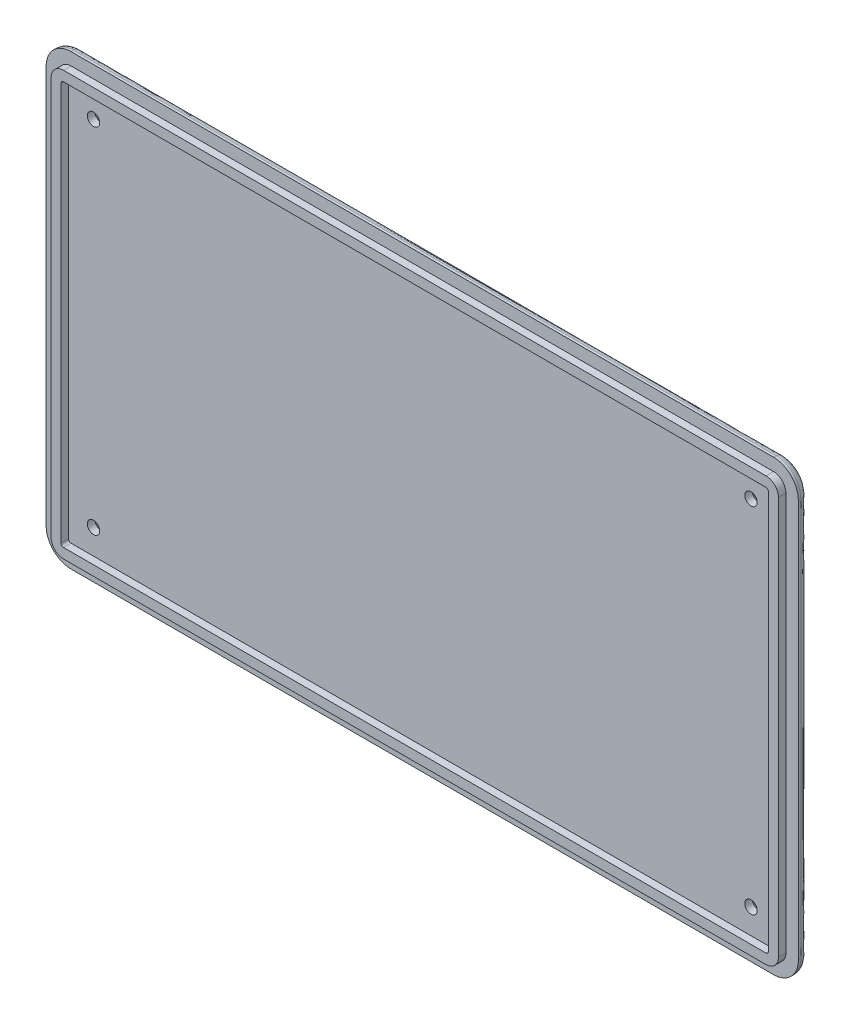
SolidWorks part; units mm, degrees
ref_plane "Спереди" through (0, 0, 0) normal (0, 0, 1) x (1, 0, 0)
ref_plane "Сверху" through (0, 0, 0) normal (0, 1, 0) x (1, 0, 0)
ref_plane "Справа" through (0, 0, 0) normal (1, 0, 0) x (0, 0, -1)
sketch "Эскиз1" plane through (0, 0, 0) normal (0, 0, 1) x (1, 0, 0)
  line L0 (-70.4628, -44.9619) -> (70.4628, -44.9619) construction
  line L1 (75.4619, -39.9628) -> (75.4619, 39.9628) construction
  line L2 (70.4628, 44.9619) -> (-70.4628, 44.9619) construction
  line L3 (-75.4619, 39.9628) -> (-75.4619, -39.9628) construction
  line L4 (-70.4628, -44.9619) -> (70.4628, -44.9619)
  line L5 (75.4619, -39.9628) -> (75.4619, 39.9628)
  line L6 (70.4628, 44.9619) -> (-70.4628, 44.9619)
  line L7 (-75.4619, 39.9628) -> (-75.4619, -39.9628)
  circle A0 centre (65.9619, -35.4619) radius 1.25 construction
  circle A1 centre (65.9619, -35.4619) radius 1.25
  circle A2 centre (65.9619, 35.4619) radius 1.25 construction
  circle A3 centre (65.9619, 35.4619) radius 1.25
  circle A4 centre (-65.9619, -35.4619) radius 1.25 construction
  circle A5 centre (-65.9619, -35.4619) radius 1.25
  circle A6 centre (-65.9619, 35.4619) radius 1.25 construction
  circle A7 centre (-65.9619, 35.4619) radius 1.25
  ellipse E0 centre (-70.4617, -39.9617) end of major axis (-66.926, -36.426) minor radius 5 (-75.4619, -39.9628) -> (-70.4628, -44.9619) ccw construction
  ellipse E1 centre (70.4617, -39.9617) end of major axis (73.9975, -43.4975) minor radius 5 (70.4628, -44.9619) -> (75.4619, -39.9628) ccw construction
  ellipse E2 centre (70.4617, 39.9617) end of major axis (66.926, 36.426) minor radius 5 (75.4619, 39.9628) -> (70.4628, 44.9619) ccw construction
  ellipse E3 centre (-70.4617, 39.9617) end of major axis (-73.9975, 43.4975) minor radius 5 (-70.4628, 44.9619) -> (-75.4619, 39.9628) ccw construction
  ellipse E4 centre (-70.4617, -39.9617) end of major axis (-66.926, -36.426) minor radius 5 (-75.4619, -39.9628) -> (-70.4628, -44.9619) ccw
  ellipse E5 centre (70.4617, -39.9617) end of major axis (73.9975, -43.4975) minor radius 5 (70.4628, -44.9619) -> (75.4619, -39.9628) ccw
  ellipse E6 centre (70.4617, 39.9617) end of major axis (66.926, 36.426) minor radius 5 (75.4619, 39.9628) -> (70.4628, 44.9619) ccw
  ellipse E7 centre (-70.4617, 39.9617) end of major axis (-73.9975, 43.4975) minor radius 5 (-70.4628, 44.9619) -> (-75.4619, 39.9628) ccw
extrude "Бобышка-Вытянуть1" add sketch "Эскиз1" against normal blind 2.5
sketch "Эскиз2" plane through (0, 0, 0) normal (0, 0, 1) x (1, 0, 0)
  line L0 (70.4628, 42.4624) -> (-70.4628, 42.4624) construction
  line L1 (72.9624, -39.9628) -> (72.9624, 39.9628) construction
  line L2 (-70.4628, -42.4624) -> (70.4628, -42.4624) construction
  line L3 (-72.9624, 39.9628) -> (-72.9624, -39.9628) construction
  line L4 (70.4628, 42.4624) -> (-70.4628, 42.4624)
  line L5 (72.9624, -39.9628) -> (72.9624, 39.9628)
  line L6 (-70.4628, -42.4624) -> (70.4628, -42.4624)
  line L7 (-72.9624, 39.9628) -> (-72.9624, -39.9628)
  line L8 (-70.9624, 39.9629) -> (-70.9624, -39.9629)
  line L9 (-70.4629, -40.4624) -> (70.4629, -40.4624)
  line L10 (70.9624, -39.9629) -> (70.9624, 39.9629)
  line L11 (70.4629, 40.4624) -> (-70.4629, 40.4624)
  ellipse E0 centre (-70.4617, 39.9617) end of major axis (-72.2304, 41.7304) minor radius 2.5 (-70.4628, 42.4624) -> (-72.9624, 39.9628) ccw construction
  ellipse E1 centre (70.4617, 39.9617) end of major axis (68.6931, 38.1931) minor radius 2.5 (72.9624, 39.9628) -> (70.4628, 42.4624) ccw construction
  ellipse E2 centre (70.4617, -39.9617) end of major axis (72.2304, -41.7304) minor radius 2.5 (70.4628, -42.4624) -> (72.9624, -39.9628) ccw construction
  ellipse E3 centre (-70.4617, -39.9617) end of major axis (-68.6931, -38.1931) minor radius 2.5 (-72.9624, -39.9628) -> (-70.4628, -42.4624) ccw construction
  ellipse E4 centre (-70.4617, 39.9617) end of major axis (-72.2304, 41.7304) minor radius 2.5 (-70.4628, 42.4624) -> (-72.9624, 39.9628) ccw
  ellipse E5 centre (70.4617, 39.9617) end of major axis (68.6931, 38.1931) minor radius 2.5 (72.9624, 39.9628) -> (70.4628, 42.4624) ccw
  ellipse E6 centre (70.4617, -39.9617) end of major axis (72.2304, -41.7304) minor radius 2.5 (70.4628, -42.4624) -> (72.9624, -39.9628) ccw
  ellipse E7 centre (-70.4617, -39.9617) end of major axis (-68.6931, -38.1931) minor radius 2.5 (-72.9624, -39.9628) -> (-70.4628, -42.4624) ccw
  spline S0 degree 1 poles (-70.9624, -39.9629) (-70.4629, -40.4624) knots 0 0 1 1 construction
  spline S1 degree 1 poles (70.4629, -40.4624) (70.9624, -39.9629) knots 0 0 1 1 construction
  spline S2 degree 1 poles (70.9624, 39.9629) (70.4629, 40.4624) knots 0 0 1 1 construction
  spline S3 degree 1 poles (-70.4629, 40.4624) (-70.9624, 39.9629) knots 0 0 1 1 construction
  spline S4 degree 3 poles (-70.9624, -39.9629) (-70.9624, -40.0904) (-70.856, -40.356) (-70.5904, -40.4624) (-70.4629, -40.4624) knots 2.356369 2.356369 2.356369 2.356369 3.141593 3.926816 3.926816 3.926816 3.926816
  spline S5 degree 3 poles (70.4629, -40.4624) (70.5904, -40.4624) (70.856, -40.356) (70.9624, -40.0904) (70.9624, -39.9629) knots -0.785224 -0.785224 -0.785224 -0.785224 0 0.785224 0.785224 0.785224 0.785224
  spline S6 degree 3 poles (70.9624, 39.9629) (70.9624, 40.0904) (70.856, 40.356) (70.5904, 40.4624) (70.4629, 40.4624) knots 2.356369 2.356369 2.356369 2.356369 3.141593 3.926816 3.926816 3.926816 3.926816
  spline S7 degree 3 poles (-70.4629, 40.4624) (-70.5904, 40.4624) (-70.856, 40.356) (-70.9624, 40.0904) (-70.9624, 39.9629) knots -0.785224 -0.785224 -0.785224 -0.785224 0 0.785224 0.785224 0.785224 0.785224
  dimension "D1" = 2
extrude "Бобышка-Вытянуть2" add sketch "Эскиз2" along normal blind 1.5
fillet "Скругление1" radius 3 8 edges at (73.9975, 43.4975, -2.5) (75.4619, 0, -2.5) (73.9975, -43.4975, -2.5) (0, -44.9619, -2.5) (-73.9975, -43.4975, -2.5) (-75.4619, 0, -2.5) (-73.9975, 43.4975, -2.5) (0, 44.9619, -2.5) second distance 2 first distance on face at (-64.7119, 35.4619, -2.5)
chamfer "Фаска1" distance 1 angle 45 4 edges at (-64.7119, 35.4619, -2.5) (-64.7119, -35.4619, -2.5) (67.2119, -35.4619, -2.5) (67.2119, 35.4619, -2.5)
